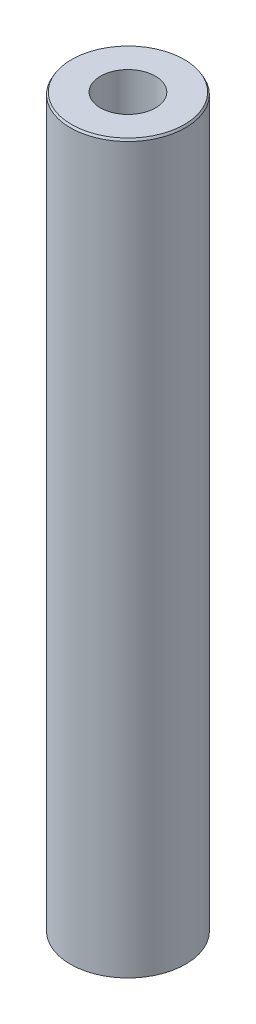
SolidWorks part; units mm, degrees
ref_plane "Front Plane" through (0, 0, 0) normal (0, 0, 1) x (1, 0, 0)
ref_plane "Top Plane" through (0, 0, 0) normal (0, 1, 0) x (1, 0, 0)
ref_plane "Right Plane" through (0, 0, 0) normal (1, 0, 0) x (0, 0, -1)
sketch "Sketch1" plane through (0, 0, 0) normal (0, 1, 0) x (1, 0, 0)
  circle A0 centre (0, 0) radius 47.5
  dimension "SHAFT_OD" = 95
extrude "Boss-Extrude1" add sketch "Sketch1" along normal blind 600
sketch "Sketch2" plane through (0, 0, 0) normal (0, 1, 0) x (1, 0, 0)
  circle A0 centre (0, 0) radius 22.6806
  dimension "BORE_D" = 45.3612
extrude "Cut-Extrude1" cut sketch "Sketch2" along normal through all
chamfer "Chamfer1" distance 1.7713 angle 30 2 edges at (0, 600, 47.5) (0, 0, 47.5) first distance on face at (0, 600, 47.5) first distance on face at (0, 0, 22.6806)
